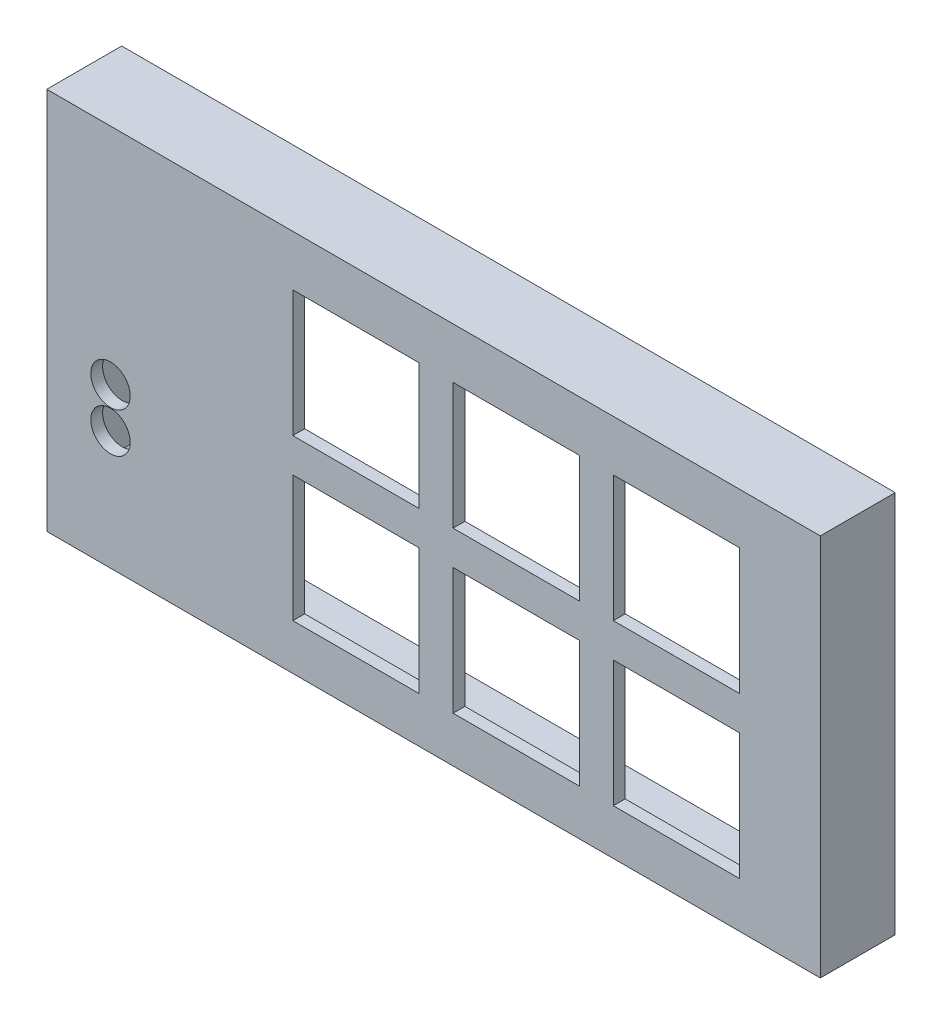
SolidWorks part; units mm, degrees
ref_plane "前视基准面" through (0, 0, 0) normal (0, 0, 1) x (1, 0, 0)
ref_plane "上视基准面" through (0, 0, 0) normal (0, 1, 0) x (1, 0, 0)
ref_plane "右视基准面" through (0, 0, 0) normal (1, 0, 0) x (0, 0, -1)
sketch "Sketch3" plane through (0, 0, 1.5) normal (0, 0, 1) x (1, 0, 0)
  line L4 (160.48, -134.445) -> (160.48, -85.9)
  line L5 (160.48, -85.9) -> (62.405, -85.9)
  line L6 (62.405, -85.9) -> (62.405, -134.445)
  line L7 (62.405, -134.445) -> (160.48, -134.445)
  line L8 (160.48, -134.445) -> (160.48, -85.9)
  line L9 (160.48, -85.9) -> (62.405, -85.9)
  line L10 (62.405, -85.9) -> (62.405, -134.445)
  line L11 (62.405, -134.445) -> (160.48, -134.445)
  line L12 (158.98, -87.4) -> (63.905, -87.4)
  line L13 (63.905, -87.4) -> (63.905, -132.945)
  line L14 (63.905, -132.945) -> (158.98, -132.945)
  line L15 (158.98, -132.945) -> (158.98, -87.4)
  line L16 (158.98, -87.4) -> (63.905, -87.4)
  line L17 (63.905, -87.4) -> (63.905, -132.945)
  line L18 (63.905, -132.945) -> (158.98, -132.945)
  line L19 (158.98, -132.945) -> (158.98, -87.4)
  dimension "D1" = 0
  dimension "D2" = 0
extrude "Wall" add sketch "Sketch3" along normal blind 9.5
sketch "Sketch4" plane through (0, 0, 11) normal (0, 0, 1) x (1, 0, 0)
  line L4 (62.405, -134.445) -> (160.48, -134.445)
  line L5 (160.48, -134.445) -> (160.48, -85.9)
  line L6 (160.48, -85.9) -> (62.405, -85.9)
  line L7 (62.405, -85.9) -> (62.405, -134.445)
  line L8 (62.405, -134.445) -> (160.48, -134.445)
  line L9 (160.48, -134.445) -> (160.48, -85.9)
  line L10 (160.48, -85.9) -> (62.405, -85.9)
  line L11 (62.405, -85.9) -> (62.405, -134.445)
  dimension "D1" = 0
extrude "TopFace" add sketch "Sketch4" against normal blind 1.5
sketch "Sketch7" plane through (0, 0, 9.5) normal (0, 0, -1) x (-1, 0, 0)
  circle A0 centre (-153.035, -93.345) radius 3
  circle A1 centre (-69.85, -93.98) radius 3
  circle A2 centre (-69.85, -127) radius 3
  circle A3 centre (-153.035, -127) radius 3
  dimension "D1" = 6
extrude "Standoffs" add sketch "Sketch7" along normal blind 8
sketch "Sketch5" plane through (0, 0, 11) normal (0, 0, 1) x (1, 0, 0)
  line L1 (150.24, -128.65) -> (134.24, -128.65)
  line L2 (150.24, -128.65) -> (150.24, -112.65)
  line L3 (150.24, -112.65) -> (134.24, -112.65)
  line L4 (134.24, -128.65) -> (134.24, -112.65)
  line L5 (150.24, -128.65) -> (134.24, -112.65) construction
  line L6 (150.24, -112.65) -> (134.24, -128.65) construction
  line L7 (129.92, -128.65) -> (113.92, -128.65)
  line L8 (129.92, -128.65) -> (129.92, -112.65)
  line L9 (129.92, -112.65) -> (113.92, -112.65)
  line L10 (113.92, -128.65) -> (113.92, -112.65)
  line L11 (129.92, -128.65) -> (113.92, -112.65) construction
  line L12 (129.92, -112.65) -> (113.92, -128.65) construction
  line L13 (109.6, -128.65) -> (93.6, -128.65)
  line L14 (109.6, -128.65) -> (109.6, -112.65)
  line L15 (109.6, -112.65) -> (93.6, -112.65)
  line L16 (93.6, -128.65) -> (93.6, -112.65)
  line L17 (109.6, -128.65) -> (93.6, -112.65) construction
  line L18 (109.6, -112.65) -> (93.6, -128.65) construction
  line L19 (109.6, -108.33) -> (93.6, -108.33)
  line L20 (109.6, -108.33) -> (109.6, -92.33)
  line L21 (109.6, -92.33) -> (93.6, -92.33)
  line L22 (93.6, -108.33) -> (93.6, -92.33)
  line L23 (109.6, -108.33) -> (93.6, -92.33) construction
  line L24 (109.6, -92.33) -> (93.6, -108.33) construction
  line L25 (150.24, -108.33) -> (134.24, -108.33)
  line L26 (150.24, -108.33) -> (150.24, -92.33)
  line L27 (150.24, -92.33) -> (134.24, -92.33)
  line L28 (134.24, -108.33) -> (134.24, -92.33)
  line L29 (150.24, -108.33) -> (134.24, -92.33) construction
  line L30 (150.24, -92.33) -> (134.24, -108.33) construction
  line L31 (113.92, -92.33) -> (129.92, -92.33)
  line L32 (113.92, -92.33) -> (113.92, -108.33)
  line L33 (113.92, -108.33) -> (129.92, -108.33)
  line L34 (129.92, -92.33) -> (129.92, -108.33)
  line L35 (113.92, -92.33) -> (129.92, -108.33) construction
  line L36 (113.92, -108.33) -> (129.92, -92.33) construction
  circle A0 centre (70.485, -114.3) radius 2.5
  circle A1 centre (70.485, -119.38) radius 2.5
  point P0 (142.24, -120.65)
  point P6 (121.92, -120.65)
  point P12 (101.6, -120.65)
  point P18 (101.6, -100.33)
  point P24 (142.24, -100.33)
  point P30 (121.92, -100.33)
  dimension "D9" = 5
  dimension "D1" = 16
  dimension "D2" = 16
  dimension "D3" = 16
  dimension "D4" = 16
  dimension "D5" = 16
  dimension "D6" = 16
  dimension "D7" = 16
  dimension "D8" = 16
extrude "KeyCut" cut sketch "Sketch5" against normal through all
